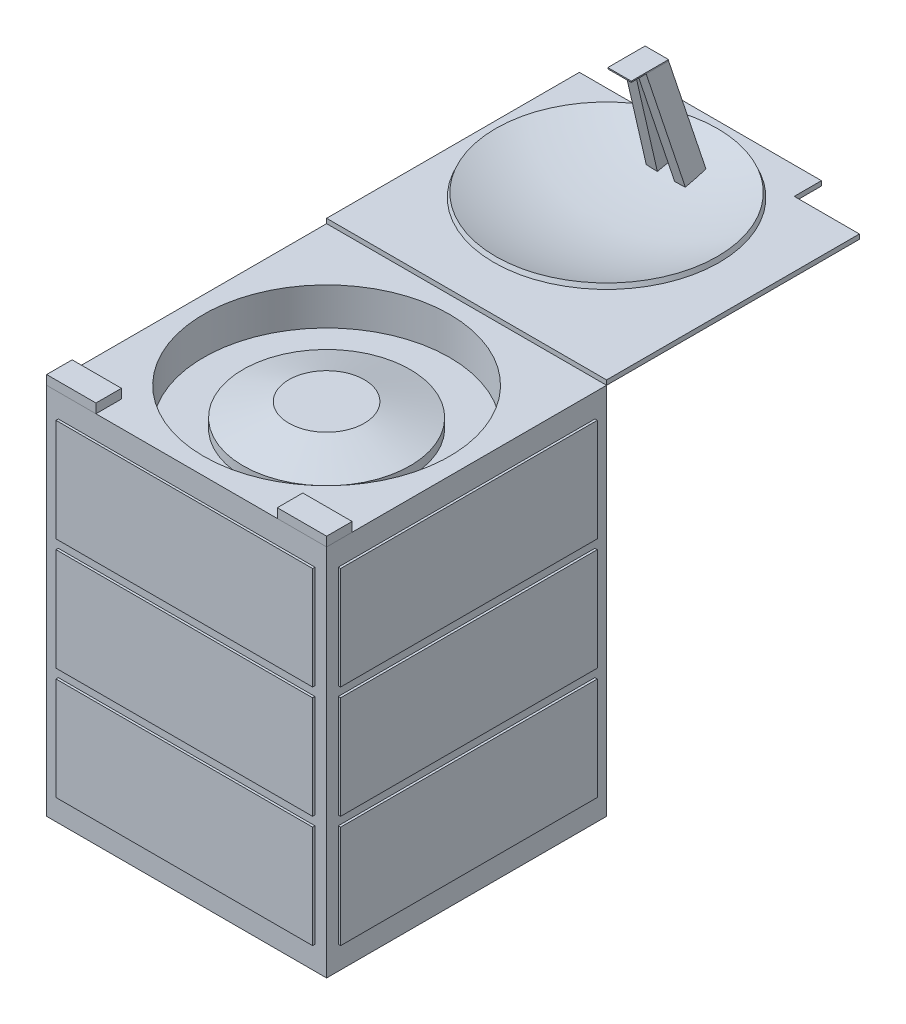
SolidWorks part; units mm, degrees
note: The reader was unsure of these and kept them because the rebuilt part matched: shared geometry of "Sketch8<7>", "Sketch9<4>".
ref_plane "Front Plane" through (0, 0, 0) normal (0, 0, 1) x (1, 0, 0)
ref_plane "Top Plane" through (0, 0, 0) normal (0, 1, 0) x (1, 0, 0)
ref_plane "Right Plane" through (0, 0, 0) normal (1, 0, 0) x (0, 0, -1)
sketch "Sketch1" plane through (0, 0, 0) normal (0, 1, 0) x (1, 0, 0)
  line L1 (300, 300) -> (-300, 300)
  line L2 (300, 300) -> (300, -300)
  line L3 (300, -300) -> (-300, -300)
  line L4 (-300, 300) -> (-300, -300)
  line L5 (300, 300) -> (-300, -300) construction
  line L6 (300, -300) -> (-300, 300) construction
  point P0 (0, 0)
  dimension "D1" = 600
  dimension "D2" = 600
extrude "Boss-Extrude1" add sketch "Sketch1" along normal blind 800
sketch "Sketch2" plane through (0, 800, 0) normal (0, 1, 0) x (1, 0, 0)
  circle A0 centre (0, 0) radius 263.5729
extrude "Cut-Extrude2" cut sketch "Sketch2" against normal blind 80
sketch "Sketch3" plane through (0, 720, 0) normal (0, 1, 0) x (1, 0, 0)
  circle A0 centre (0, 0) radius 178.9891
extrude "Boss-Extrude2" add sketch "Sketch3" along normal blind 50
chamfer "Chamfer1" distance 30 angle 73 1 edges at (0, 770, 178.9891)
sketch "Sketch4" plane through (0, 800, 0) normal (0, 1, 0) x (1, 0, 0)
  line L1 (300, 300) -> (-300, 300)
  line L2 (300, 300) -> (300, 900)
  line L3 (300, 900) -> (-300, 900)
  line L4 (-300, 300) -> (-300, 900)
  dimension "D1" = 600
  dimension "D2" = 600
extrude "Boss-Extrude3" add sketch "Sketch4" along normal blind 10 separate body
sketch "Sketch5" plane through (0, 810, 0) normal (0, 1, 0) x (1, 0, 0)
  line L0 (0, 0) -> (0, 778.7179) construction
  line L1 (300, 900) -> (160.4258, 900)
  line L2 (300, 900) -> (300, 841.7219)
  line L3 (300, 841.7219) -> (160.4258, 841.7219)
  line L4 (160.4258, 900) -> (160.4258, 841.7219)
  line L5 (-160.4258, 900) -> (-160.4258, 841.7219)
  line L6 (-300, 841.7219) -> (-160.4258, 841.7219)
  line L7 (-300, 900) -> (-300, 841.7219)
  line L8 (-300, 900) -> (-160.4258, 900)
extrude "Cut-Extrude3" cut sketch "Sketch5" against normal through all both and the other way through all
sketch "Sketch7" plane through (0, 0, 0) normal (1, 0, 0) x (0, 0, -1)
  line L0 (600, 533.3011) -> (600, 1035.5411) construction
  line L1 (300, 800) -> (300, 0) construction
  arc A0 (600, 810) -> (837.5943, 857.8347) centre (600, 1423.9817) ccw
  point P7 (0, 0)
  point P9 (0, 0)
  point P10 (0, 0)
  dimension "D1" = 300
revolve "Revolve-Thin1" add sketch "Sketch7" angle 360 about L0
sketch "Sketch8" plane through (0, 810, 0) normal (0, 1, 0) x (1, 0, 0)
  line L1 (-19.464, 731.2667) -> (-42.9573, 731.2667)
  line L2 (19.464, 779.3213) -> (42.9573, 779.3213)
  line L3 (19.464, 779.3213) -> (19.464, 731.2667)
  line L4 (19.464, 731.2667) -> (42.9573, 731.2667)
  line L5 (42.9573, 779.3213) -> (42.9573, 731.2667)
  line L6 (-42.9573, 779.3213) -> (-42.9573, 731.2667)
  line L7 (-19.464, 779.3213) -> (-42.9573, 779.3213)
  line L8 (-19.464, 779.3213) -> (-19.464, 731.2667)
ref_plane "Plane1" through (0, 1060, 0) normal (0, 1, 0) x (1, 0, 0)
sketch "Sketch9" plane through (0, 1060, 0) normal (0, 1, 0) x (1, 0, 0)
  line L0 (0.8975, 708.4776) -> (24.3909, 708.4776)
  line L5 (0.8975, 708.4776) -> (0.8975, 660.423)
  line L6 (0.8975, 660.423) -> (24.3909, 660.423)
  line L7 (24.3909, 708.4776) -> (24.3909, 660.423)
  line L8 (-25.9458, 708.6503) -> (-2.4525, 708.6503)
  line L9 (-25.9458, 708.6503) -> (-25.9458, 660.5957)
  line L10 (-25.9458, 660.5957) -> (-2.4525, 660.5957)
  line L11 (-2.4525, 708.6503) -> (-2.4525, 660.5957)
loft "Loft2" add section "Sketch8" section "Sketch9"
loft "Loft3" add section "Sketch8<7>" section "Sketch9<4>"
sketch "Sketch8<7>" plane through (0, 810, 0) normal (0, 1, 0) x (1, 0, 0) same geometry as "Sketch8"
sketch "Sketch9<4>" plane through (0, 1060, 0) normal (0, 1, 0) x (1, 0, 0) same geometry as "Sketch9"
sketch "Sketch10" plane through (0, 0, 0) normal (1, 0, 0) x (0, 0, -1)
  line L0 (720.9349, 810) -> (787.5615, 810)
  line L1 (841.7219, 810) -> (300, 810) construction
  line L2 (787.5615, 810) -> (784.0867, 827.7726)
  line L3 (784.0867, 827.7726) -> (720.9349, 811.8315)
  line L4 (720.9349, 811.8315) -> (720.9349, 810)
  arc A0 (358.5359, 848.6138) -> (841.4641, 848.6138) centre (600, 1423.9817) ccw construction
  arc A1 (358.5359, 848.6138) -> (841.4641, 848.6138) centre (600, 1423.9817) ccw construction
revolve "Cut-Revolve1" cut sketch "Sketch10" angle 360 about L0
sketch "Sketch11" plane through (0, 1060, 0) normal (0, 1, 0) x (1, 0, 0)
  line L0 (-25.9458, 708.6503) -> (-25.9458, 660.5957) construction
  line L1 (24.3909, 708.4776) -> (-25.9458, 708.4776)
  line L2 (24.3909, 708.4776) -> (24.3909, 628.4776)
  line L3 (24.3909, 628.4776) -> (-25.9458, 628.4776)
  line L4 (-25.9458, 708.4776) -> (-25.9458, 628.4776)
  dimension "D1" = 0
  dimension "D2" = 80
extrude "Boss-Extrude4" add sketch "Sketch11" along normal blind 2.5
sketch "Sketch12" plane through (-300, 0, 0) normal (-1, 0, 0) x (0, 0, 1)
  line L0 (-300, 800) -> (-300, 0) construction
  line L1 (-275, 750) -> (275, 750)
  line L2 (-275, 750) -> (-275, 530)
  line L3 (-275, 530) -> (275, 530)
  line L4 (275, 750) -> (275, 530)
  line L5 (-275, 510) -> (-275, 290)
  line L6 (-275, 510) -> (275, 510)
  line L7 (275, 510) -> (275, 290)
  line L8 (-275, 290) -> (275, 290)
  line L9 (-275, 270) -> (-275, 50)
  line L10 (-275, 270) -> (275, 270)
  line L11 (275, 270) -> (275, 50)
  line L12 (-275, 50) -> (275, 50)
  line L13 (-300, 800) -> (300, 800) construction
  dimension "D1" = 550
  dimension "D2" = 25
  dimension "D3" = 220
  dimension "D5" = 50
  dimension "D4" = 3
extrude "Boss-Extrude5" add sketch "Sketch12" along normal blind 5 contours L2 L1 L4 L3 | L5 L8 L7 L6 | L9 L12 L11 L10
mirror "Mirror1" about plane through (0, 0, 0) normal (1, 0, 0) of "Boss-Extrude5"
sketch "Sketch13" plane through (0, 0, 300) normal (0, 0, 1) x (1, 0, 0)
  line L0 (-275, 750) -> (275, 750)
  line L1 (-275, 750) -> (-275, 530)
  line L2 (-275, 530) -> (275, 530)
  line L3 (275, 750) -> (275, 530)
  line L4 (-275, 510) -> (-275, 290)
  line L5 (-275, 510) -> (275, 510)
  line L6 (275, 510) -> (275, 290)
  line L7 (-275, 290) -> (275, 290)
  line L8 (-275, 270) -> (-275, 50)
  line L9 (-275, 270) -> (275, 270)
  line L10 (275, 270) -> (275, 50)
  line L11 (-275, 50) -> (275, 50)
  line L13 (-300, 800) -> (300, 800) construction
  line L15 (-300, 800) -> (-300, 0) construction
  dimension "D1" = 550
  dimension "D2" = 20
  dimension "D3" = 20
  dimension "D4" = 220
  dimension "D5" = 220
  dimension "D6" = 220
  dimension "D7" = 550
  dimension "D8" = 550
  dimension "D9" = 50
  dimension "D10" = 25
extrude "Boss-Extrude6" add sketch "Sketch13" along normal blind 5
mirror "Mirror2" about plane through (0, 0, 0) normal (0, 0, 1) of "Boss-Extrude6"
sketch "Sketch14" plane through (0, 800, 0) normal (0, 1, 0) x (1, 0, 0)
  line L0 (0, 0) -> (0, -339.1193) construction
  line L1 (300, -300) -> (194.3186, -300)
  line L2 (300, -300) -> (300, -245.3493)
  line L3 (300, -245.3493) -> (194.3186, -245.3493)
  line L4 (194.3186, -300) -> (194.3186, -245.3493)
  line L5 (-194.3186, -300) -> (-194.3186, -245.3493)
  line L6 (-300, -245.3493) -> (-194.3186, -245.3493)
  line L7 (-300, -300) -> (-300, -245.3493)
  line L8 (-300, -300) -> (-194.3186, -300)
extrude "Boss-Extrude7" add sketch "Sketch14" along normal blind 20 separate body
